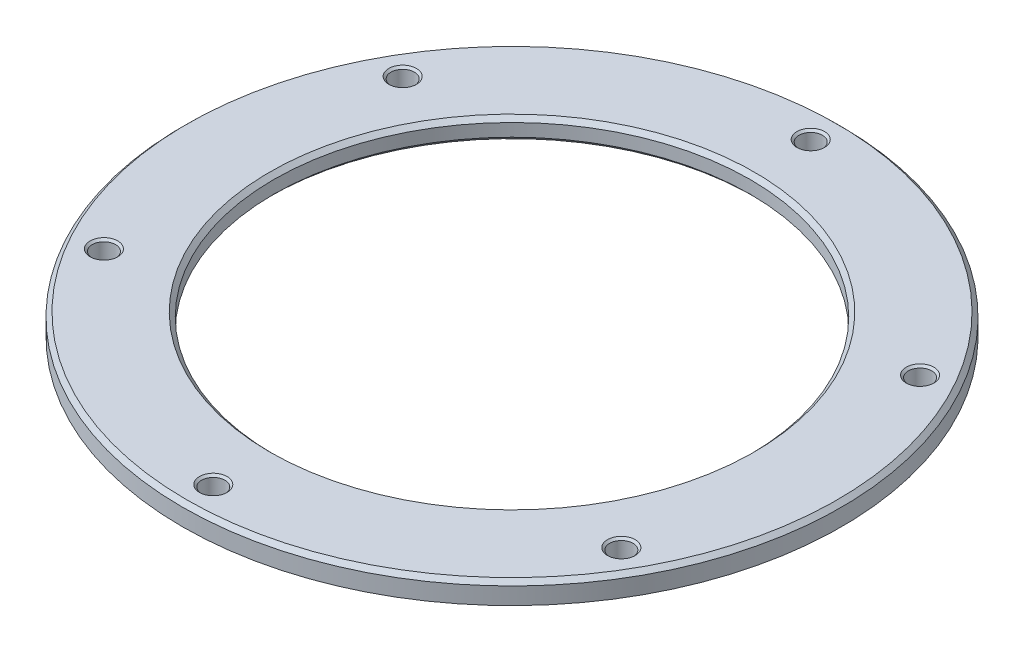
SolidWorks part; units mm, degrees
material "0.6010 (EN-GJL-100)"
ref_plane "Front Plane" through (0, 0, 0) normal (0, 0, 1) x (1, 0, 0)
ref_plane "Top Plane" through (0, 0, 0) normal (0, 1, 0) x (1, 0, 0)
ref_plane "Right Plane" through (0, 0, 0) normal (1, 0, 0) x (0, 0, -1)
sketch "Sketch1" plane through (0, 0, 0) normal (0, 1, 0) x (1, 0, 0)
  circle A0 centre (0, 0) radius 77.5
  circle A1 centre (0, 0) radius 56
  dimension "D1" = 155
  dimension "D2" = 112
extrude "Boss-Extrude1" add sketch "Sketch1" along normal blind 5
sketch "Sketch2" plane through (0, 5, 0) normal (0, 1, 0) x (1, 0, 0)
  circle A0 centre (0, 70.25) radius 2.75
  dimension "D1" = 5.5
  dimension "D2" = 70.25
extrude "Cut-Extrude2" cut sketch "Sketch2" against normal through all contours A0
chamfer "Chamfer1" distance 0.5 angle 45 2 edges at (0, 5, -67.5) (0, 0, -67.5)
pattern_circular "CirPattern1" count 6 over 360 about axis through (0, 5, 0) along (0, -1, 0) of "Cut-Extrude2", "Chamfer1" reverse direction yes
chamfer "Chamfer2" distance 1 angle 45 3 edges at (0, 5, 77.5) (0, 0, 56) (0, 5, 56)
